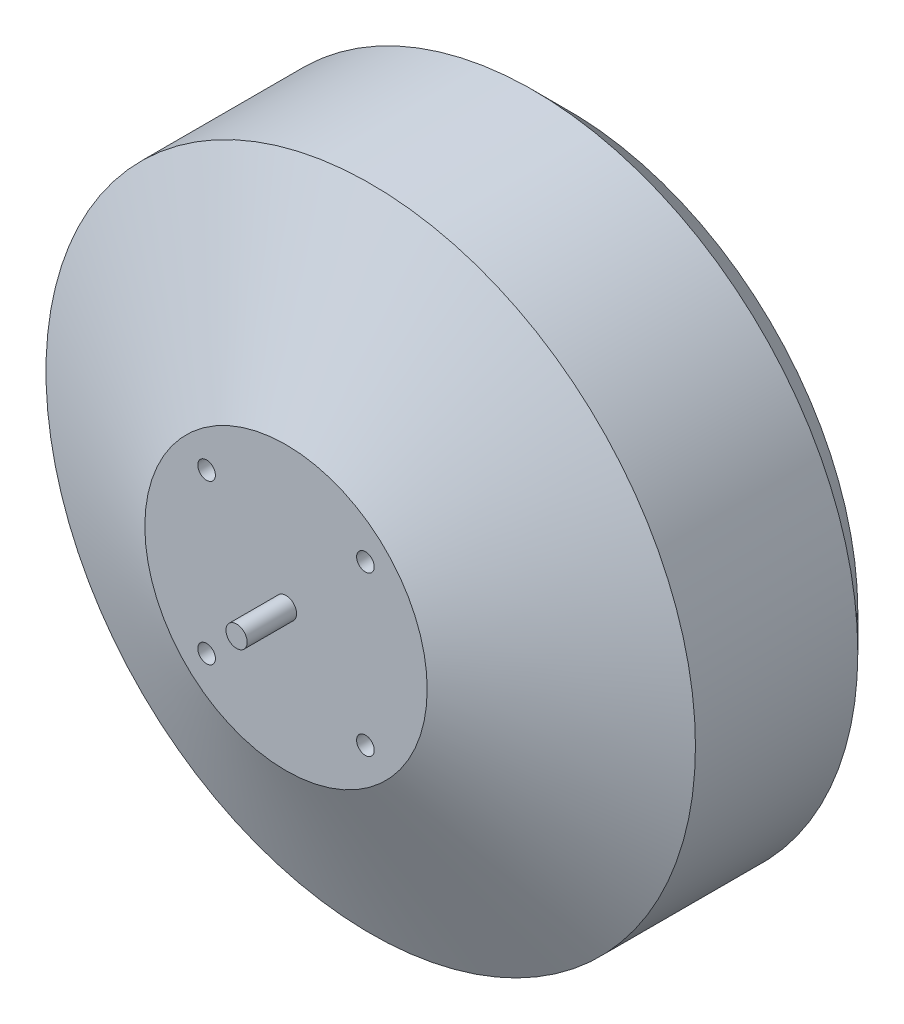
SolidWorks part; units mm, degrees
ref_plane "Front Plane" through (0, 0, 0) normal (0, 0, 1) x (1, 0, 0)
ref_plane "Top Plane" through (0, 0, 0) normal (0, 1, 0) x (1, 0, 0)
ref_plane "Right Plane" through (0, 0, 0) normal (1, 0, 0) x (0, 0, -1)
sketch "Sketch1" plane through (0, 0, 0) normal (1, 0, 0) x (0, 0, -1)
  line L0 (0, 46) -> (-28, 46)
  line L1 (-28, 46) -> (-40, 20)
  line L2 (-40, 20) -> (-40, 0)
  line L3 (-1764.481, 0) -> (86459.5709, 0) construction
  line L4 (0, 46) -> (0, 0)
  line L5 (-40, 0) -> (0, 0)
  dimension "D1" = 92
  dimension "D2" = 40
  dimension "D3" = 40
  dimension "D4" = 28
revolve "Body" add sketch "Sketch1" angle 360 about L3
sketch "Sketch2" plane through (0, 0, 40) normal (0, 0, 1) x (1, 0, 0)
  line L1 (11.25, -11.25) -> (-11.25, -11.25) construction
  line L2 (11.25, -11.25) -> (11.25, 11.25) construction
  line L3 (11.25, 11.25) -> (-11.25, 11.25) construction
  line L4 (-11.25, -11.25) -> (-11.25, 11.25) construction
  line L5 (11.25, -11.25) -> (-11.25, 11.25) construction
  line L6 (11.25, 11.25) -> (-11.25, -11.25) construction
  circle A0 centre (-11.25, 11.25) radius 1.25
  circle A1 centre (11.25, 11.25) radius 1.25
  circle A2 centre (11.25, -11.25) radius 1.25
  circle A3 centre (-11.25, -11.25) radius 1.25
  point P0 (0, 0)
  dimension "D2" = 2.5
  dimension "D1" = 22.5
extrude "Rotor_Holes" cut sketch "Sketch2" against normal blind 10
sketch "Sketch4" plane through (0, 0, 0) normal (0, 0, -1) x (-1, 0, 0)
  line L1 (14.25, -14.25) -> (-14.25, -14.25) construction
  line L2 (14.25, -14.25) -> (14.25, 14.25) construction
  line L3 (14.25, 14.25) -> (-14.25, 14.25) construction
  line L4 (-14.25, -14.25) -> (-14.25, 14.25) construction
  line L5 (14.25, -14.25) -> (-14.25, 14.25) construction
  line L6 (14.25, 14.25) -> (-14.25, -14.25) construction
  circle A0 centre (-14.25, 14.25) radius 1.75
  circle A1 centre (14.25, 14.25) radius 1.75
  circle A2 centre (14.25, -14.25) radius 1.75
  circle A3 centre (-14.25, -14.25) radius 1.75
  point P0 (0, 0)
  dimension "D2" = 3.5
  dimension "D1" = 28.5
extrude "Stator_Holes" cut sketch "Sketch4" against normal blind 10
sketch "Sketch5" plane through (0, 0, 0) normal (0, 0, -1) x (-1, 0, 0)
  circle A0 centre (0, 0) radius 1.75
  dimension "D1" = 3.5
extrude "Hole" cut sketch "Sketch5" against normal blind 5
fillet "Fillet1" radius 1 1 edges at (-1.75, 0, 0)
sketch "Sketch6" plane through (0, 0, 40) normal (0, 0, 1) x (1, 0, 0)
  circle A0 centre (0, 0) radius 1.5
  dimension "D1" = 3
extrude "Shaft" add sketch "Sketch6" along normal blind 7
chamfer "Chamfer1" distance 5 angle 45 1 edges at (46, 0, 0)
